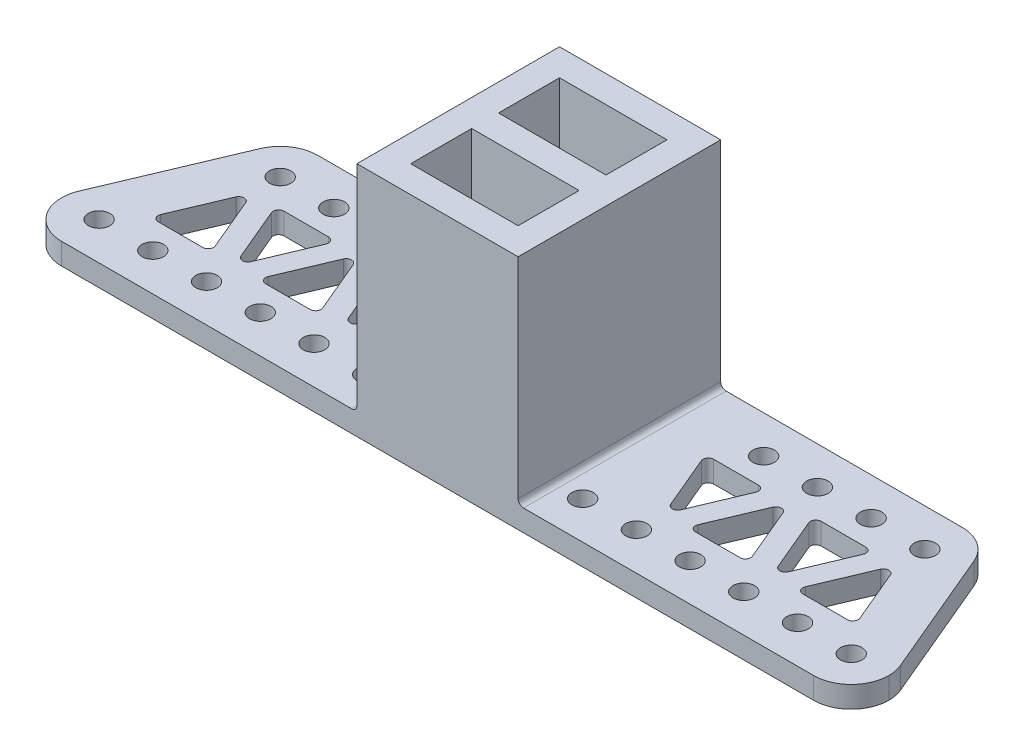
SolidWorks part; units mm, degrees
ref_plane "前视基准面" through (0, 0, 0) normal (0, 0, 1) x (1, 0, 0)
ref_plane "上视基准面" through (0, 0, 0) normal (0, 1, 0) x (1, 0, 0)
ref_plane "右视基准面" through (0, 0, 0) normal (1, 0, 0) x (0, 0, -1)
other "Configuration Table"
sketch "草图1" plane through (0, 0, 0) normal (0, 1, 0) x (1, 0, 0)
  line L1 (-77, 18.85) -> (77, 18.85)
  line L2 (-77, 18.85) -> (-77, -18.85)
  line L3 (-77, -18.85) -> (77, -18.85)
  line L4 (77, 18.85) -> (77, -18.85)
  line L5 (-77, 18.85) -> (77, -18.85) construction
  line L6 (-77, -18.85) -> (77, 18.85) construction
  point P0 (0, 0)
  dimension "D1" = 154
  dimension "D2" = 37.7
extrude "凸台-拉伸1" add sketch "草图1" against normal blind 4
sketch "草图2" plane through (0, 0, 0) normal (0, 1, 0) x (1, 0, 0)
  line L0 (0, 18.85) -> (0, -18.85) construction
  line L1 (77, 18.85) -> (-77, 18.85) construction
  line L2 (-77, -18.85) -> (77, -18.85) construction
  line L3 (-30, 0) -> (-30, 11.85) construction
  line L4 (-77, 18.85) -> (-77, -18.85) construction
  line L5 (-77, 0) -> (0, 0) construction
  line L6 (-20, 0) -> (-20, -11.85) construction
  circle A0 centre (-30, 11.85) radius 2
  circle A1 centre (-20, -11.85) radius 2
  circle A2 centre (-40, 11.85) radius 2
  circle A3 centre (-50, 11.85) radius 2
  circle A4 centre (-60, 11.85) radius 2
  circle A5 centre (-30, -11.85) radius 2
  circle A6 centre (-40, -11.85) radius 2
  circle A7 centre (-50, -11.85) radius 2
  circle A8 centre (-60, -11.85) radius 2
  circle A9 centre (-70, -11.85) radius 2
  circle A10 centre (20, -11.85) radius 2
  circle A11 centre (30, -11.85) radius 2
  circle A12 centre (40, -11.85) radius 2
  circle A13 centre (50, -11.85) radius 2
  circle A14 centre (60, -11.85) radius 2
  circle A15 centre (70, -11.85) radius 2
  circle A16 centre (30, 11.85) radius 2
  circle A17 centre (40, 11.85) radius 2
  circle A18 centre (50, 11.85) radius 2
  circle A19 centre (60, 11.85) radius 2
  dimension "D5" = 4
  dimension "D6" = 4
  dimension "D1" = 11.85
  dimension "D2" = 30
  dimension "D3" = 11.85
  dimension "D4" = 20
  dimension "D8" = 10
  dimension "D10" = 10
  dimension "D7" = 4
  dimension "D9" = 6
extrude "切除-拉伸1" cut sketch "草图2" against normal through all both and the other way through all
sketch "草图3" plane through (0, 0, 0) normal (0, 1, 0) x (1, 0, 0)
  line L0 (-60, 11.85) -> (-70, -11.85) construction
  line L1 (-64.644, 18.85) -> (-77, -10.4337)
  line L2 (77, 18.85) -> (-77, 18.85) construction
  line L3 (-77, 18.85) -> (-77, -18.85) construction
  line L4 (-64.644, 18.85) -> (-77, 18.85)
  line L5 (-77, 18.85) -> (-77, -10.4337)
  line L6 (0, 18.85) -> (0, -18.85) construction
  line L7 (-77, -18.85) -> (77, -18.85) construction
  line L8 (64.644, 18.85) -> (77, -10.4337)
  line L9 (77, 18.85) -> (77, -10.4337)
  line L10 (64.644, 18.85) -> (77, 18.85)
  dimension "D1" = 7
extrude "切除-拉伸2" cut sketch "草图3" against normal through all both and the other way through all
fillet "圆角1" radius 7 6 edges at (77, -2, 18.85) (64.644, -2, -18.85) (-77, -2, 18.85) (-64.644, -2, -18.85)
sketch "草图4" plane through (0, 0, 0) normal (0, 1, 0) x (1, 0, 0)
  line L0 (0, 18.85) -> (0, -18.85) construction
  line L1 (60, 18.85) -> (-60, 18.85) construction
  line L2 (-70, -18.85) -> (70, -18.85) construction
  line L4 (-15, 18.85) -> (15, 18.85)
  line L5 (-15, 18.85) -> (-15, -18.85)
  line L6 (-15, -18.85) -> (15, -18.85)
  line L7 (15, 18.85) -> (15, -18.85)
  point P10 (0, 0)
  dimension "D1" = 30
extrude "凸台-拉伸2" add sketch "草图4" along normal blind 40
sketch "草图5" plane through (0, 0, 0) normal (0, 1, 0) x (1, 0, 0)
  line L0 (-15, 0) -> (15, 0) construction
  line L1 (-15, 18.85) -> (-15, -18.85) construction
  line L2 (15, -18.85) -> (15, 18.85) construction
  line L3 (15, 18.85) -> (-15, 18.85) construction
  line L4 (-10, 13.85) -> (10, 13.85)
  line L5 (-10, 13.85) -> (-10, 2.5)
  line L6 (-10, 2.5) -> (10, 2.5)
  line L7 (10, 13.85) -> (10, 2.5)
  line L8 (-10, -13.85) -> (-10, -2.5)
  line L9 (-10, -2.5) -> (10, -2.5)
  line L10 (10, -13.85) -> (10, -2.5)
  line L11 (-10, -13.85) -> (10, -13.85)
  point P10 (0, 2.5)
  dimension "D1" = 20
  dimension "D2" = 2.5
  dimension "D3" = 5
extrude "切除-拉伸3" cut sketch "草图5" along normal through all both and the other way through all
sketch "草图6" plane through (0, 0, 0) normal (0, 1, 0) x (1, 0, 0)
  line L0 (-58.1573, 11.0725) -> (-68.1573, -12.6275) construction
  line L1 (-61.8427, 11.0725) -> (-51.8427, -12.6275) construction
  line L2 (-34.3415, -6.7053) -> (-40, 6.7053)
  line L3 (-40, 6.7053) -> (-45.6585, -6.7053)
  line L4 (-55.6585, 6.7053) -> (-50, -6.7053)
  line L5 (-60, 6.7053) -> (-65.6585, -6.7053)
  line L6 (-65.6585, -6.7053) -> (-54.3415, -6.7053)
  line L7 (-54.3415, -6.7053) -> (-60, 6.7053)
  line L8 (-60, 6.7053) -> (-60, -6.7053) construction
  line L9 (-50, -6.7053) -> (-44.3415, 6.7053)
  line L10 (-45.6585, -6.7053) -> (-34.3415, -6.7053)
  line L11 (-44.3415, 6.7053) -> (-55.6585, 6.7053)
  line L12 (-35.6585, 6.7053) -> (-30, -6.7053)
  line L13 (-30, -6.7053) -> (-24.3415, 6.7053)
  line L14 (-24.3415, 6.7053) -> (-35.6585, 6.7053)
  line L15 (0, 18.85) -> (0, -18.85) construction
  line L16 (15, 18.85) -> (-15, 18.85) construction
  line L17 (-15, -18.85) -> (15, -18.85) construction
  line L18 (24.3415, 6.7053) -> (35.6585, 6.7053)
  line L19 (30, -6.7053) -> (24.3415, 6.7053)
  line L20 (35.6585, 6.7053) -> (30, -6.7053)
  line L21 (45.6585, -6.7053) -> (34.3415, -6.7053)
  line L22 (40, 6.7053) -> (45.6585, -6.7053)
  line L23 (34.3415, -6.7053) -> (40, 6.7053)
  line L24 (44.3415, 6.7053) -> (55.6585, 6.7053)
  line L25 (50, -6.7053) -> (44.3415, 6.7053)
  line L26 (55.6585, 6.7053) -> (50, -6.7053)
  line L27 (65.6585, -6.7053) -> (54.3415, -6.7053)
  line L28 (60, 6.7053) -> (65.6585, -6.7053)
  line L29 (54.3415, -6.7053) -> (60, 6.7053)
  circle A0 centre (-60, 11.85) radius 2 construction
  circle A1 centre (-70, -11.85) radius 2 construction
  circle A2 centre (-50, -11.85) radius 2 construction
  point P10 (-60, 0)
  point P11 (-40, 11.85)
  point P20 (-50, -11.85)
  point P33 (-55, 0)
  dimension "D2" = 2
  dimension "D1" = 2
extrude "切除-拉伸4" cut sketch "草图6" against normal through all both and the other way through all
fillet "圆角2" radius 1 24 edges at (65.6585, -2, 6.7053) (54.3415, -2, 6.7053) (60, -2, -6.7053) (55.6585, -2, -6.7053) (50, -2, 6.7053) (44.3415, -2, -6.7053) (45.6585, -2, 6.7053) (34.3415, -2, 6.7053) (40, -2, -6.7053) (30, -2, 6.7053) (35.6585, -2, -6.7053) (24.3415, -2, -6.7053) (-30, -2, 6.7053) (-24.3415, -2, -6.7053) (-35.6585, -2, -6.7053) (-34.3415, -2, 6.7053) (-45.6585, -2, 6.7053) (-40, -2, -6.7053) (-50, -2, 6.7053) (-44.3415, -2, -6.7053) (-55.6585, -2, -6.7053) (-54.3415, -2, 6.7053) (-65.6585, -2, 6.7053) (-60, -2, -6.7053)
fillet "圆角4" radius 1 2 edges at (15, 0, 0) (-15, 0, 0)
